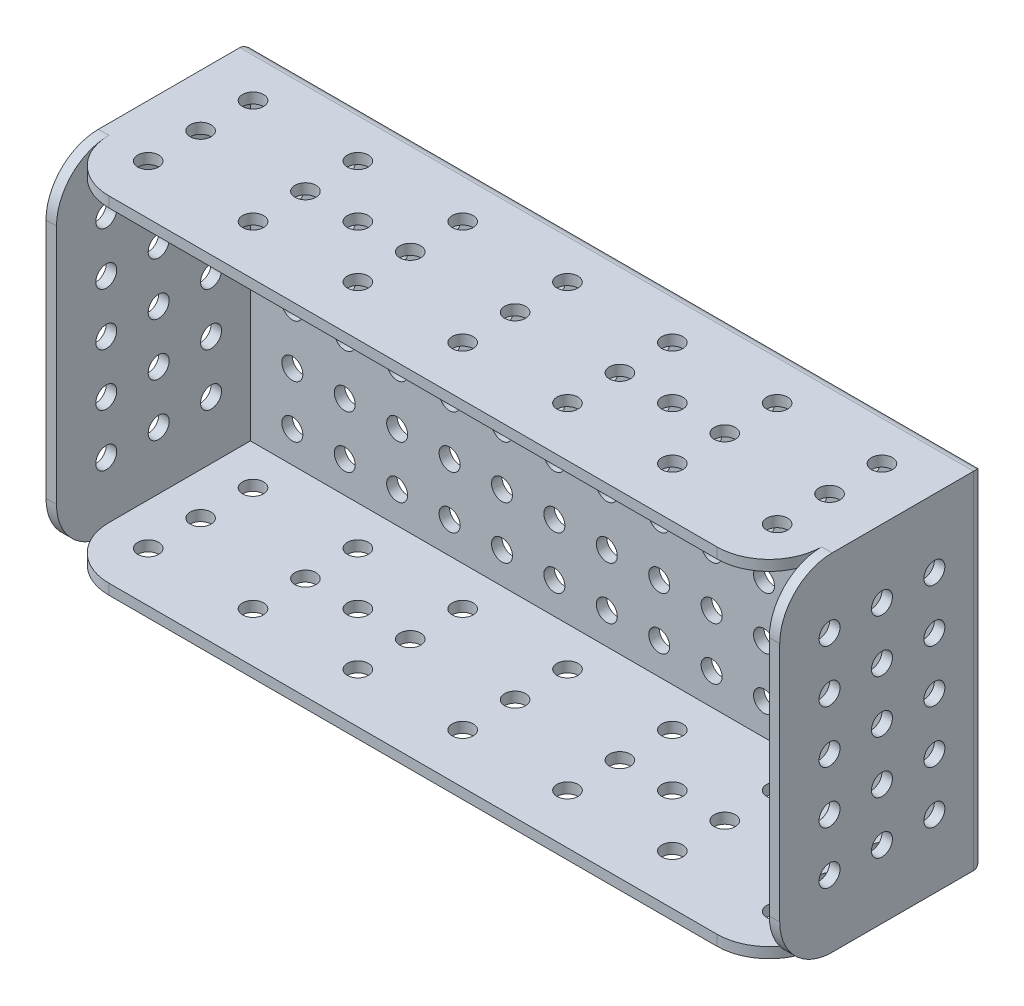
SolidWorks part; units mm, degrees
material "6061-T6 (SS)"
ref_plane "Ön Düzlem" through (0, 0, 0) normal (0, 0, 1) x (1, 0, 0)
ref_plane "Üst Düzlem" through (0, 0, 0) normal (0, 1, 0) x (1, 0, 0)
ref_plane "Sağ Düzlem" through (0, 0, 0) normal (1, 0, 0) x (0, 0, -1)
sketch "Çizim1" plane through (0, 0, 0) normal (0, 0, 1) x (1, 0, 0)
  line L1 (-72.7036, 33.3533) -> (67.2964, 33.3533)
  line L2 (-72.7036, 33.3533) -> (-72.7036, -32.6467)
  line L3 (-72.7036, -32.6467) -> (67.2964, -32.6467)
  line L4 (67.2964, 33.3533) -> (67.2964, -32.6467)
  dimension "D1" = 140
  dimension "D2" = 66
extrude "Yükseklik-Ekstrüzyon1" add sketch "Çizim1" along normal blind 2
sketch "Çizim2" plane through (0, 0, 2) normal (0, 0, 1) x (1, 0, 0)
  line L0 (-72.7036, -32.6467) -> (67.2964, -32.6467) construction
  line L1 (-72.7036, 33.3533) -> (-70.7036, 33.3533)
  line L2 (-72.7036, 33.3533) -> (-72.7036, -32.6467)
  line L3 (-72.7036, -32.6467) -> (-70.7036, -32.6467)
  line L4 (-70.7036, 33.3533) -> (-70.7036, -32.6467)
  line L6 (67.2964, 33.3533) -> (65.2964, 33.3533)
  line L7 (67.2964, 33.3533) -> (67.2964, -32.6467)
  line L8 (67.2964, -32.6467) -> (65.2964, -32.6467)
  line L9 (65.2964, 33.3533) -> (65.2964, -32.6467)
  dimension "D1" = 2
  dimension "D2" = 2
extrude "Yükseklik-Ekstrüzyon2" add sketch "Çizim2" along normal blind 37
fillet "Radyus1" radius 10 4 edges at (-71.7036, -32.6467, 39) (66.2964, -32.6467, 39) (66.2964, 33.3533, 39) (-71.7036, 33.3533, 39)
sketch "Çizim3" plane through (0, 0, 2) normal (0, 0, 1) x (1, 0, 0)
  line L0 (65.2964, 33.3533) -> (65.2964, -32.6467) construction
  line L1 (-70.7036, 33.3533) -> (65.2964, 33.3533)
  line L2 (-70.7036, 33.3533) -> (-70.7036, 31.3533)
  line L3 (-70.7036, 31.3533) -> (65.2964, 31.3533)
  line L4 (65.2964, 33.3533) -> (65.2964, 31.3533)
  line L6 (-70.7036, -32.6467) -> (65.2964, -32.6467)
  line L7 (-70.7036, -32.6467) -> (-70.7036, -30.6467)
  line L8 (-70.7036, -30.6467) -> (65.2964, -30.6467)
  line L9 (65.2964, -32.6467) -> (65.2964, -30.6467)
  dimension "D1" = 2
  dimension "D2" = 2
extrude "Yükseklik-Ekstrüzyon3" add sketch "Çizim3" along normal blind 37
fillet "Radyus2" radius 10 4 edges at (-70.7036, -31.6467, 39) (65.2964, -31.6467, 39) (65.2964, 32.3533, 39) (-70.7036, 32.3533, 39)
sketch "Çizim4" plane through (0, 0, 0) normal (0, 0, -1) x (-1, 0, 0)
  line L0 (-67.2964, -32.6467) -> (-67.2964, 33.3533) construction
  line L1 (-67.2964, 33.3533) -> (72.7036, 33.3533) construction
  circle A0 centre (-57.2964, 25.3533) radius 2
  circle A1 centre (-47.2964, 25.3533) radius 2
  circle A2 centre (-37.2964, 25.3533) radius 2
  circle A3 centre (-27.2964, 25.3533) radius 2
  circle A4 centre (-17.2964, 25.3533) radius 2
  circle A5 centre (-7.2964, 25.3533) radius 2
  circle A6 centre (2.7036, 25.3533) radius 2
  circle A7 centre (12.7036, 25.3533) radius 2
  circle A8 centre (22.7036, 25.3533) radius 2
  circle A9 centre (32.7036, 25.3533) radius 2
  circle A10 centre (42.7036, 25.3533) radius 2
  circle A11 centre (52.7036, 25.3533) radius 2
  circle A12 centre (62.7036, 25.3533) radius 2
  circle A13 centre (-47.2964, 15.3533) radius 2
  circle A14 centre (-37.2964, 15.3533) radius 2
  circle A15 centre (-27.2964, 15.3533) radius 2
  circle A16 centre (-17.2964, 15.3533) radius 2
  circle A17 centre (-7.2964, 15.3533) radius 2
  circle A18 centre (2.7036, 15.3533) radius 2
  circle A19 centre (12.7036, 15.3533) radius 2
  circle A20 centre (22.7036, 15.3533) radius 2
  circle A21 centre (32.7036, 15.3533) radius 2
  circle A22 centre (42.7036, 15.3533) radius 2
  circle A23 centre (52.7036, 15.3533) radius 2
  circle A24 centre (62.7036, 15.3533) radius 2
  circle A25 centre (-47.2964, 5.3533) radius 2
  circle A26 centre (-37.2964, 5.3533) radius 2
  circle A27 centre (-27.2964, 5.3533) radius 2
  circle A28 centre (-17.2964, 5.3533) radius 2
  circle A29 centre (-7.2964, 5.3533) radius 2
  circle A30 centre (2.7036, 5.3533) radius 2
  circle A31 centre (12.7036, 5.3533) radius 2
  circle A32 centre (22.7036, 5.3533) radius 2
  circle A33 centre (32.7036, 5.3533) radius 2
  circle A34 centre (42.7036, 5.3533) radius 2
  circle A35 centre (52.7036, 5.3533) radius 2
  circle A36 centre (62.7036, 5.3533) radius 2
  circle A37 centre (-47.2964, -4.6467) radius 2
  circle A38 centre (-37.2964, -4.6467) radius 2
  circle A39 centre (-27.2964, -4.6467) radius 2
  circle A40 centre (-17.2964, -4.6467) radius 2
  circle A41 centre (-7.2964, -4.6467) radius 2
  circle A42 centre (2.7036, -4.6467) radius 2
  circle A43 centre (12.7036, -4.6467) radius 2
  circle A44 centre (22.7036, -4.6467) radius 2
  circle A45 centre (32.7036, -4.6467) radius 2
  circle A46 centre (42.7036, -4.6467) radius 2
  circle A47 centre (52.7036, -4.6467) radius 2
  circle A48 centre (62.7036, -4.6467) radius 2
  circle A49 centre (-47.2964, -14.6467) radius 2
  circle A50 centre (-37.2964, -14.6467) radius 2
  circle A51 centre (-27.2964, -14.6467) radius 2
  circle A52 centre (-17.2964, -14.6467) radius 2
  circle A53 centre (-7.2964, -14.6467) radius 2
  circle A54 centre (2.7036, -14.6467) radius 2
  circle A55 centre (12.7036, -14.6467) radius 2
  circle A56 centre (22.7036, -14.6467) radius 2
  circle A57 centre (32.7036, -14.6467) radius 2
  circle A58 centre (42.7036, -14.6467) radius 2
  circle A59 centre (52.7036, -14.6467) radius 2
  circle A60 centre (62.7036, -14.6467) radius 2
  circle A61 centre (-47.2964, -24.6467) radius 2
  circle A62 centre (-37.2964, -24.6467) radius 2
  circle A63 centre (-27.2964, -24.6467) radius 2
  circle A64 centre (-17.2964, -24.6467) radius 2
  circle A65 centre (-7.2964, -24.6467) radius 2
  circle A66 centre (2.7036, -24.6467) radius 2
  circle A67 centre (12.7036, -24.6467) radius 2
  circle A68 centre (22.7036, -24.6467) radius 2
  circle A69 centre (32.7036, -24.6467) radius 2
  circle A70 centre (42.7036, -24.6467) radius 2
  circle A71 centre (52.7036, -24.6467) radius 2
  circle A72 centre (62.7036, -24.6467) radius 2
  circle A73 centre (-57.2964, 15.3533) radius 2
  circle A74 centre (-57.2964, 5.3533) radius 2
  circle A75 centre (-57.2964, -4.6467) radius 2
  circle A76 centre (-57.2964, -14.6467) radius 2
  circle A77 centre (-57.2964, -24.6467) radius 2
  dimension "D1" = 4
  dimension "D3" = 10
  dimension "D2" = 8
  dimension "D4" = 13
  dimension "D5" = 6
extrude "Kes-Ekstrüzyon1" cut sketch "Çizim4" against normal blind 37
sketch "Çizim6" plane through (-72.7036, 0, 0) normal (-1, 0, 0) x (0, 0, 1)
  line L0 (29, -32.6467) -> (0, -32.6467) construction
  line L2 (0, 33.3533) -> (0, -32.6467) construction
  circle A0 centre (9.5, -19.6467) radius 2
  circle A1 centre (19.5, -19.6467) radius 2
  circle A2 centre (29.5, -19.6467) radius 2
  circle A3 centre (19.5, -9.6467) radius 2
  circle A4 centre (29.5, -9.6467) radius 2
  circle A5 centre (19.5, 0.3533) radius 2
  circle A6 centre (29.5, 0.3533) radius 2
  circle A7 centre (19.5, 10.3533) radius 2
  circle A8 centre (29.5, 10.3533) radius 2
  circle A9 centre (19.5, 20.3533) radius 2
  circle A10 centre (29.5, 20.3533) radius 2
  circle A11 centre (9.5, -9.6467) radius 2
  circle A12 centre (9.5, 0.3533) radius 2
  circle A13 centre (9.5, 10.3533) radius 2
  circle A14 centre (9.5, 20.3533) radius 2
  dimension "D1" = 4
  dimension "D2" = 13
  dimension "D5" = 9.5
  dimension "D3" = 3
  dimension "D4" = 5
extrude "Kes-Ekstrüzyon2" cut sketch "Çizim6" against normal through all
sketch "Çizim7" plane through (0, 33.3533, 0) normal (0, 1, 0) x (1, 0, 0)
  line L0 (67.2964, 0) -> (-72.7036, 0) construction
  line L1 (-72.7036, -29) -> (-72.7036, 0) construction
  circle A0 centre (-62.7036, -9.5) radius 2
  circle A1 centre (-42.7036, -9.5) radius 2
  circle A2 centre (-22.7036, -9.5) radius 2
  circle A3 centre (-2.7036, -9.5) radius 2
  circle A4 centre (17.2964, -9.5) radius 2
  circle A5 centre (37.2964, -9.5) radius 2
  circle A6 centre (57.2964, -9.5) radius 2
  circle A7 centre (-42.7036, -19.5) radius 2
  circle A8 centre (-22.7036, -19.5) radius 2
  circle A9 centre (-2.7036, -19.5) radius 2
  circle A10 centre (17.2964, -19.5) radius 2
  circle A11 centre (37.2964, -19.5) radius 2
  circle A12 centre (57.2964, -19.5) radius 2
  circle A13 centre (-42.7036, -29.5) radius 2
  circle A14 centre (-22.7036, -29.5) radius 2
  circle A15 centre (-2.7036, -29.5) radius 2
  circle A16 centre (17.2964, -29.5) radius 2
  circle A17 centre (37.2964, -29.5) radius 2
  circle A18 centre (57.2964, -29.5) radius 2
  circle A19 centre (-62.7036, -19.5) radius 2
  circle A20 centre (-62.7036, -29.5) radius 2
  circle A21 centre (-32.7036, -19.5) radius 2
  circle A22 centre (27.2964, -19.5) radius 2
  dimension "D1" = 4
  dimension "D2" = 9.5
  dimension "D3" = 10
  dimension "D6" = 4
  dimension "D7" = 4
  dimension "D8" = 30
  dimension "D9" = 10
  dimension "D4" = 7
  dimension "D5" = 3
extrude "Kes-Ekstrüzyon3" cut sketch "Çizim7" against normal through all
fillet "Radyus3" radius 2 4 edges at (-2.7036, 33.3533, 0) (-72.7036, 0.3533, 0) (-2.7036, -32.6467, 0) (67.2964, 0.3533, 0)
